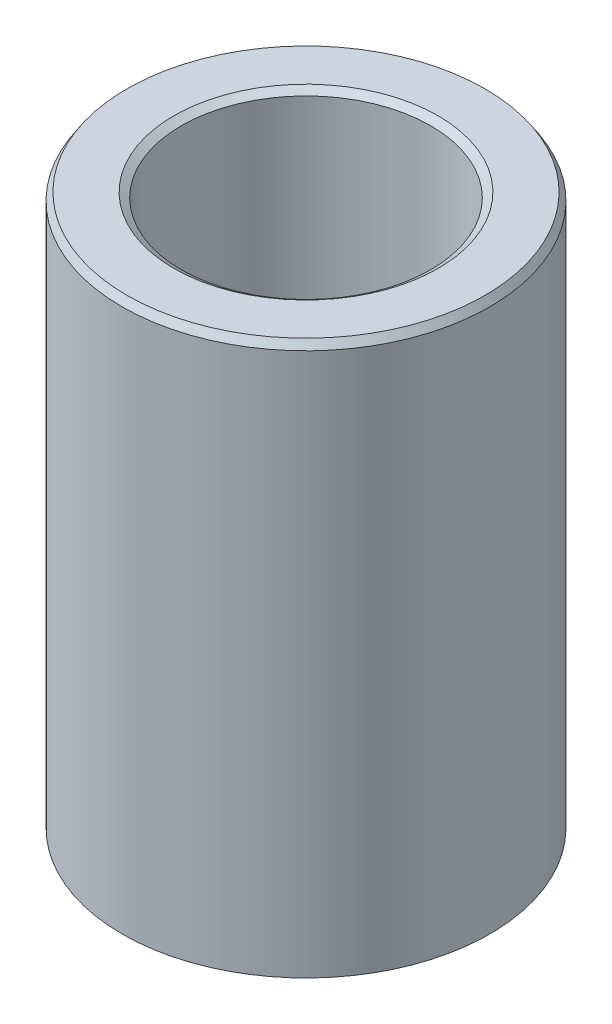
SolidWorks part; units mm, degrees
ref_plane "Front Plane" through (0, 0, 0) normal (0, 0, 1) x (1, 0, 0)
ref_plane "Top Plane" through (0, 0, 0) normal (0, 1, 0) x (1, 0, 0)
ref_plane "Right Plane" through (0, 0, 0) normal (1, 0, 0) x (0, 0, -1)
sketch "Sketch1" plane through (0, 0, 0) normal (0, 1, 0) x (1, 0, 0)
  circle A0 centre (0, 0) radius 10
  dimension "SLEEVE_OD" = 20
extrude "Boss-Extrude1" add sketch "Sketch1" along normal blind 30.2189
sketch "Sketch2" plane through (0, 0, 0) normal (0, 1, 0) x (1, 0, 0)
  circle A0 centre (0, 0) radius 6.7832
  dimension "BORE_D" = 13.5664
extrude "Cut-Extrude1" cut sketch "Sketch2" along normal through all
chamfer "Chamfer1" distance 0.4074 angle 33.038 4 edges at (0, 30.2189, 6.7832) (0, 0, 6.7832) (0, 0, 10) (0, 30.2189, 10) first distance on face at (0, 30.2189, 6.7832) first distance on face at (0, 0, 6.7832) first distance on face at (0, 30.2189, 10)
